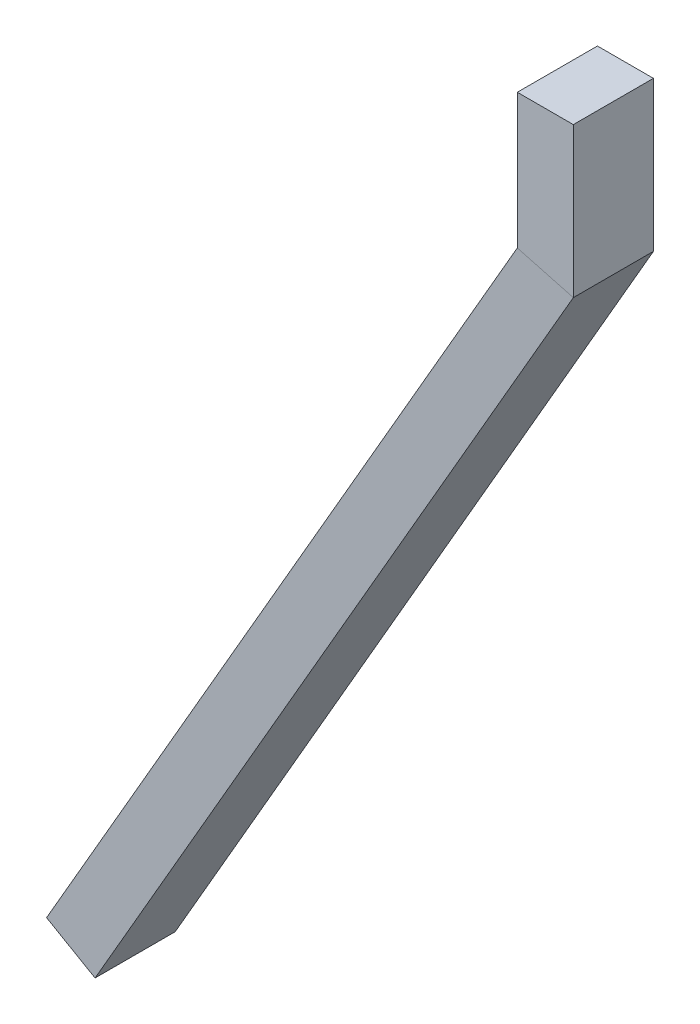
SolidWorks part; units mm, degrees
ref_plane "Plan de face" through (0, 0, 0) normal (0, 0, 1) x (1, 0, 0)
ref_plane "Plan de dessus" through (0, 0, 0) normal (0, 1, 0) x (1, 0, 0)
ref_plane "Plan de droite" through (0, 0, 0) normal (1, 0, 0) x (0, 0, -1)
sketch "Esquisse1" plane through (0, 0, 0) normal (0, 0, 1) x (1, 0, 0)
  line L0 (0, 0) -> (0, -3)
  line L1 (0, -3) -> (-10, -20.3205)
  dimension "D1" = 3
  dimension "D2" = 20
  dimension "D3" = 30
sketch "Esquisse3" plane through (0, 0, 0) normal (0, 1, 0) x (1, 0, 0)
  line L0 (-0.5901, 0) -> (0.5901, 0)
  line L1 (-0.5901, 0) -> (-0.5901, 1.6883)
  line L2 (0.5901, 0) -> (0.5901, 1.6883)
  line L3 (-0.5901, 1.6883) -> (0.5901, 1.6883)
  line L4 (0, 0) -> (-10, 0) construction
  point P7 (0, 0)
sweep "Balayage2" add profiles "Esquisse3" path "Esquisse1"
sketch "Esquisse4" plane through (0, 0, 0) normal (0, 0, 1) x (1, 0, 0)
  line L0 (0, -3) -> (10, -20.3205)
  line L1 (0.5901, -3.1581) -> (-0.5901, -2.8419) construction
  line L2 (-10.511, -20.0255) -> (-9.489, -20.6156) construction
  point P4 (9.5406, -20.5777)
  point P5 (0, 0)
  point P8 (-10, -20.3205)
  dimension "D1" = 20
sketch "Esquisse5" plane through (0, 0, 0) normal (0, 1, 0) x (1, 0, 0)
  line L0 (0, 0) -> (0, 2.7954)
equation "\"tunnel\"=3"
equation "\"D1@Esquisse1\"=\"tunnel\""
equation "\"losange_long\"=20"
equation "\"D2@Esquisse1\"=\"losange_long\""
equation "\"losange_angle\"=30"
equation "\"D3@Esquisse1\"=\"losange_angle\""
equation "\"D1@Esquisse4\"=\"losange_long\""
